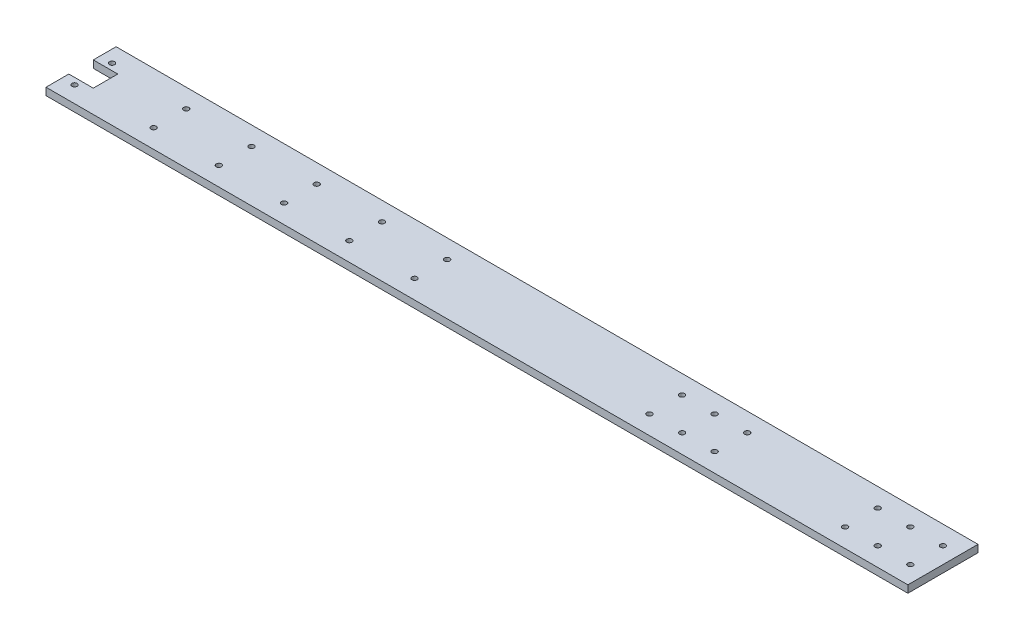
SolidWorks part; units mm, degrees
ref_plane "Front Plane" through (0, 0, 0) normal (0, 0, 1) x (1, 0, 0)
ref_plane "Top Plane" through (0, 0, 0) normal (0, 1, 0) x (1, 0, 0)
ref_plane "Right Plane" through (0, 0, 0) normal (1, 0, 0) x (0, 0, -1)
sketch "Sketch1" plane through (0, 0, 0) normal (0, 1, 0) x (1, 0, 0)
  line L0 (-264.25, 0) -> (-5.75, 0) construction
  line L1 (-264.25, -21.5) -> (264.25, -21.5)
  line L2 (-264.25, -21.5) -> (-264.25, 21.5)
  line L3 (-264.25, 21.5) -> (264.25, 21.5)
  line L4 (264.25, -21.5) -> (264.25, 21.5)
  line L5 (-264.25, -21.5) -> (264.25, 21.5) construction
  line L6 (-264.25, 21.5) -> (264.25, -21.5) construction
  line L7 (-5.75, -35) -> (-5.75, 35) construction
  line L8 (-5.75, 21.5) -> (-5.75, -21.5) construction
  circle A0 centre (-209.75, 10) radius 1.6
  circle A2 centre (-169.75, 10) radius 1.6
  circle A3 centre (-129.75, 10) radius 1.6
  circle A4 centre (-89.75, 10) radius 1.6
  circle A5 centre (-49.75, 10) radius 1.6
  circle A8 centre (-169.75, -10) radius 1.6
  circle A9 centre (-129.75, -10) radius 1.6
  circle A10 centre (-89.75, -10) radius 1.6
  circle A11 centre (-49.75, -10) radius 1.6
  circle A14 centre (-209.75, -10) radius 1.6
  circle A15 centre (234.25, 10) radius 1.6
  circle A16 centre (114.25, 10) radius 1.6
  circle A17 centre (114.25, -10) radius 1.6
  circle A18 centre (234.25, -10) radius 1.6
  circle A19 centre (134.25, -10) radius 1.6
  circle A20 centre (134.25, 10) radius 1.6
  circle A21 centre (254.25, 10) radius 1.6
  circle A22 centre (254.25, -10) radius 1.6
  circle A23 centre (94.25, -10) radius 1.6
  circle A24 centre (94.25, 10) radius 1.6
  circle A25 centre (214.25, 10) radius 1.6
  circle A26 centre (214.25, -10) radius 1.6
  point P0 (0, 0)
  dimension "D4" = 3.2
  dimension "D5" = 5
  dimension "D1" = 528.5
  dimension "D2" = 43
  dimension "D3" = 10
  dimension "D7" = 54.5
  dimension "D8" = 30
  dimension "D9" = 240
  dimension "D6" = 2
  dimension "D10" = 2
  dimension "D11" = 2
  dimension "D12" = 2
  dimension "D13" = 2
extrude "Boss-Extrude1" add sketch "Sketch1" along normal blind 4.5
sketch "Sketch2" plane through (0, 4.5, 0) normal (0, 1, 0) x (1, 0, 0)
  line L0 (-264.25, 0) -> (-249.25, 0) construction
  line L1 (-264.25, 21.5) -> (-264.25, -21.5) construction
  line L2 (-264.25, -7.5) -> (-249.25, -7.5)
  line L3 (-264.25, 7.5) -> (-249.25, 7.5)
  line L4 (-264.25, -7.5) -> (-264.25, 7.5)
  line L5 (-249.25, -7.5) -> (-249.25, 7.5)
  line L6 (-256.75, 0) -> (-256.75, 11.5) construction
  circle A4 centre (-256.75, 11.5) radius 1.6
  circle A5 centre (-256.75, -11.5) radius 1.6
  dimension "D5" = 3.2
  dimension "D1" = 15
  dimension "D4" = 4
  dimension "D2" = 7.5
  dimension "D3" = 7.5
extrude "Cut-Extrude1" cut sketch "Sketch2" against normal through all
